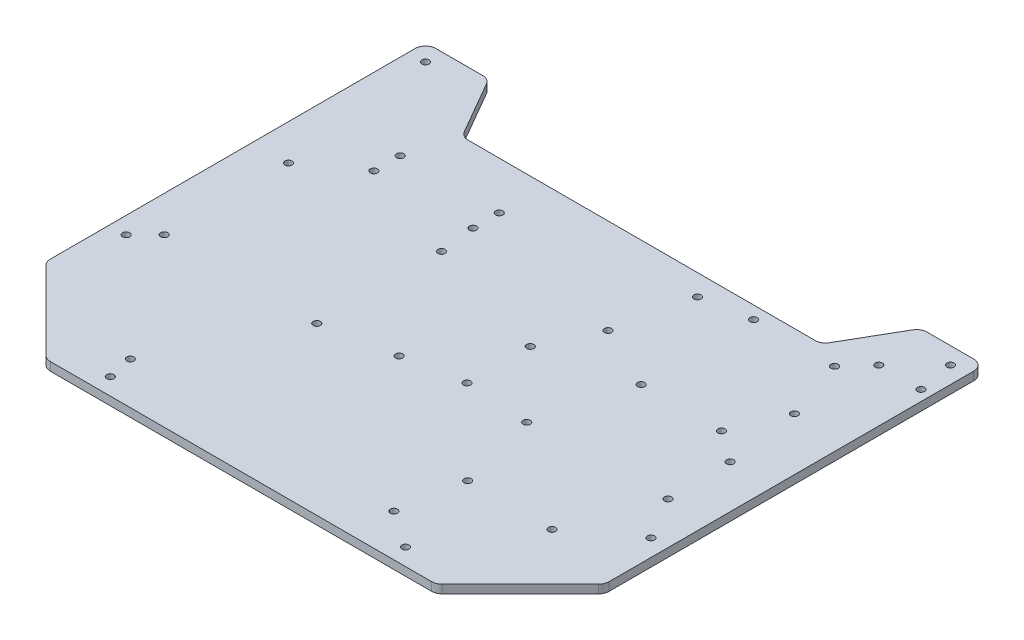
SolidWorks part; units mm, degrees
material "Acier non allié"
ref_plane "Front" through (0, 0, 0) normal (0, 0, 1) x (1, 0, 0)
ref_plane "Top" through (0, 0, 0) normal (0, 1, 0) x (1, 0, 0)
ref_plane "Right" through (0, 0, 0) normal (1, 0, 0) x (0, 0, -1)
sketch "Main scetch" plane through (0, 0, 0) normal (0, 1, 0) x (1, 0, 0)
  line L1 (0, 0) -> (132.5, 0) construction
  line L2 (0, 0) -> (0, 220) construction
  line L3 (0, 220) -> (132.5, 220) construction
  line L4 (132.5, 0) -> (132.5, 220) construction
  line L13 (-92.5, 0) -> (92.5, 0)
  line L14 (92.5, 0) -> (132.5, 40)
  line L15 (132.5, 40) -> (132.5, 220)
  line L16 (132.5, 220) -> (102.5, 220)
  line L17 (102.5, 220) -> (85.1795, 190)
  line L18 (85.1795, 190) -> (-85.1795, 190)
  line L19 (-102.5, 220) -> (-85.1795, 190)
  line L20 (-132.5, 220) -> (-102.5, 220)
  line L21 (-132.5, 40) -> (-132.5, 220)
  line L22 (-92.5, 0) -> (-132.5, 40)
  point P11 (0, 190)
  dimension "132.5" = 132.5
  dimension "D2" = 220
  dimension "D1" = 40
  dimension "D3" = 40
  dimension "D4" = 30
  dimension "D5" = 60
  dimension "D6" = 30
extrude "Main extrusion" add sketch "Main scetch" along normal blind 4
fillet "Congé1" radius 5 10 edges at (-132.5, 2, -40) (-92.5, 2, 0) (92.5, 2, 0) (132.5, 2, -40) (132.5, 2, -220) (102.5, 2, -220) (85.1795, 2, -190) (-85.1795, 2, -190) (-102.5, 2, -220) (-132.5, 2, -220)
sketch "Esquisse1" plane through (0, 4, 0) normal (0, 1, 0) x (1, 0, 0)
  line L0 (0, 0) -> (0, 218.5516) construction
  line L1 (132.5, 42.0711) -> (132.5, 215) construction
  line L2 (127.5, 220) -> (105.3868, 220) construction
  line L3 (-90.4289, 0) -> (90.4289, 0) construction
  circle A0 centre (70, 8) radius 1
  circle A1 centre (124.5, 70) radius 1
  circle A2 centre (124.5, 212) radius 1
  circle A3 centre (-124.5, 212) radius 1
  circle A4 centre (-124.5, 70) radius 1
  circle A5 centre (-70, 8) radius 1
  dimension "D1" = 2
  dimension "D2" = 2
  dimension "D3" = 2
  dimension "D4" = 8
  dimension "D5" = 8
  dimension "D6" = 8
  dimension "D7" = 8
  dimension "D8" = 70
  dimension "D9" = 70
extrude "Enlèv. mat.-Extru.1" cut sketch "Esquisse1" against normal through all
hole_wizard "Dégagement M31" positions "Esquisse2" profile "Esquisse3" hole size "M3" standard "ISO" end condition through all
sketch "Esquisse2" plane through (0, 4, 0) normal (0, 1, 0) x (1, 0, 0)
  point P0 (-124.5, 212)
  point P3 (-124.5, 70)
  point P6 (-70, 8)
  point P9 (70, 8)
  point P12 (124.5, 70)
  point P15 (124.5, 212)
sketch "Esquisse3" plane through (-124.5, 4, -212) normal (1, 0, 0) x (0, 0, 1)
  line L0 (0, 0) -> (0, 4)
  line L1 (0, 4) -> (1.7, 4)
  line L2 (1.7, 4) -> (1.7, 0)
  line L5 (1.7, 0) -> (0, 0)
  line L11 (0, -6.35) -> (0, 107.95) construction
  dimension "Diamètre du perçage jusqu'au prochain" = 3.4
  dimension "Profondeur du perçage jusqu'au prochain" = 4
sketch "Esquisse4" plane through (0, 4, 0) normal (0, 1, 0) x (1, 0, 0)
  line L0 (-132.5, 215) -> (-132.5, 42.0711) construction
  line L2 (82.2927, 190) -> (-82.2927, 190) construction
  line L3 (132.5, 42.0711) -> (132.5, 215) construction
  line L4 (-90.4289, 0) -> (90.4289, 0) construction
  line L5 (127.5, 220) -> (105.3868, 220) construction
  line L6 (59.15, 184) -> (97.5, 184) construction
  line L8 (59.15, 130.66) -> (97.25, 130.66) construction
  circle A1 centre (-68.5, 185) radius 1 construction
  circle A5 centre (36.5, 180) radius 1
  circle A6 centre (29.12, 145) radius 1
  circle A7 centre (107.5, 155) radius 1
  circle A8 centre (127.5, 195) radius 1
  circle A9 centre (112, 120) radius 1
  circle A10 centre (112.5, 90) radius 1
  circle A11 centre (17.2, 120) radius 1
  circle A12 centre (17.2, 90) radius 1
  circle A13 centre (47.5, 88) radius 1
  circle A14 centre (57.5, 50) radius 1
  circle A15 centre (97.5, 50) radius 1
  circle A16 centre (52.5, 20) radius 1
  circle A17 centre (-10, 85) radius 1
  circle A18 centre (-72.5, 20) radius 1
  circle A19 centre (107.5, 195) radius 1
  circle A23 centre (-115.5, 138) radius 1
  circle A24 centre (-42.86, 138) radius 1
  circle A25 centre (-115.5, 79.07) radius 1
  circle A26 centre (-42.8904, 78.82) radius 1
  circle A27 centre (-92, 167.5) radius 1
  circle A28 centre (-45, 167.5) radius 1
  circle A29 centre (-92, 155) radius 1
  circle A30 centre (-45, 155) radius 1
  circle A31 centre (59.15, 184) radius 1
  circle A32 centre (97.5, 184) radius 1
  circle A33 centre (59.15, 130.66) radius 1
  circle A34 centre (97.25, 130.66) radius 1
  point P66 (0, 0)
  dimension "D4" = 2
  dimension "D13" = 2
  dimension "D16" = 2
  dimension "D19" = 2
  dimension "D24" = 2
  dimension "D25" = 2
  dimension "D28" = 2
  dimension "D30" = 2
  dimension "D32" = 2
  dimension "D36" = 2
  dimension "D37" = 2
  dimension "D40" = 2
  dimension "D48" = 2
  dimension "D49" = 2
  dimension "D50" = 2
  dimension "D52" = 2
  dimension "D11" = 2
  dimension "D12" = 2
  dimension "D65" = 2
  dimension "D66" = 2
  dimension "D58" = 2
  dimension "D61" = 2
  dimension "D70" = 2
  dimension "D71" = 2
  dimension "D74" = 2
  dimension "D75" = 2
  dimension "D76" = 2
  dimension "D77" = 2
  dimension "D14" = 169
  dimension "D15" = 10
  dimension "D17" = 161.62
  dimension "D18" = 45
  dimension "D20" = 25
  dimension "D21" = 65
  dimension "D22" = 5
  dimension "D23" = 25
  dimension "D26" = 20.5
  dimension "D27" = 100
  dimension "D29" = 30
  dimension "D31" = 115.3
  dimension "D33" = 115.3
  dimension "D34" = 132
  dimension "D35" = 85
  dimension "D38" = 50
  dimension "D39" = 75
  dimension "D41" = 35
  dimension "D42" = 80
  dimension "D43" = 20
  dimension "D44" = 20
  dimension "D45" = 205
  dimension "D46" = 85
  dimension "D47" = 142.5
  dimension "D51" = 25
  dimension "D53" = 25
  dimension "D54" = 5
  dimension "D55" = 64
  dimension "D7" = 59.18
  dimension "D8" = 72.64
  dimension "D9" = 58.93
  dimension "D10" = 72.61
  dimension "D67" = 17
  dimension "D68" = 138
  dimension "D56" = 23.5
  dimension "D57" = 23.5
  dimension "D59" = 17.5
  dimension "D60" = 17.5
  dimension "D62" = 12.5
  dimension "D63" = 12.5
  dimension "D64" = 23.5
  dimension "D69" = 23.5
  dimension "D72" = 53.34
  dimension "D73" = 38.35
  dimension "D78" = 6
  dimension "D79" = 38.1
  dimension "D80" = 73.35
  dimension "D81" = 73.35
extrude "Enlèv. mat.-Extru.2" cut sketch "Esquisse4" against normal through all
hole_wizard "Dégagement M32" positions "Esquisse5" profile "Esquisse6" hole size "M3" standard "ISO" end condition through all
sketch "Esquisse5" plane through (0, 4, 0) normal (0, 1, 0) x (1, 0, 0)
  point P9 (17.2, 120)
  point P18 (29.12, 145)
  point P21 (36.5, 180)
  point P24 (107.5, 155)
  point P27 (127.5, 195)
  point P30 (112, 120)
  point P33 (112.5, 90)
  point P36 (47.5, 88)
  point P39 (17.2, 90)
  point P42 (57.5, 50)
  point P45 (97.5, 50)
  point P48 (-10, 85)
  point P51 (-72.5, 20)
  point P54 (52.5, 20)
  point P57 (107.5, 195)
  point P86 (-115.5, 138)
  point P89 (-42.86, 138)
  point P92 (-115.5, 79.07)
  point P95 (-42.8904, 78.82)
  point P102 (-92, 167.5)
  point P105 (-92, 155)
  point P108 (-45, 155)
  point P111 (-45, 167.5)
  point P114 (59.15, 184)
  point P117 (97.5, 184)
  point P120 (59.15, 130.66)
  point P123 (97.25, 130.66)
sketch "Esquisse6" plane through (17.2, 4, -120) normal (1, 0, 0) x (0, 0, 1)
  line L0 (0, 0) -> (0, 4)
  line L1 (0, 4) -> (1.7, 4)
  line L2 (1.7, 4) -> (1.7, 0)
  line L5 (1.7, 0) -> (0, 0)
  line L11 (0, -6.35) -> (0, 107.95) construction
  dimension "Diamètre du perçage jusqu'au prochain" = 3.4
  dimension "Profondeur du perçage jusqu'au prochain" = 4
equation "\"WIDTH\"= 300mm'Total width of the robot"
equation "\"LENGTH\"= 220mm'Total length of the robot"
equation "\"D2@Main scetch\" = \"LENGTH\""
equation "\"CUT_DEPTH\"= 45mm'Depth of the cut on the edges of the plate"
equation "\"Plate_th\"= 3mm'Thickness of the plate"
equation "\"D1\"= \"Plate_th\""
equation "\"D47@Esquisse4\"=(80+205)/2"
